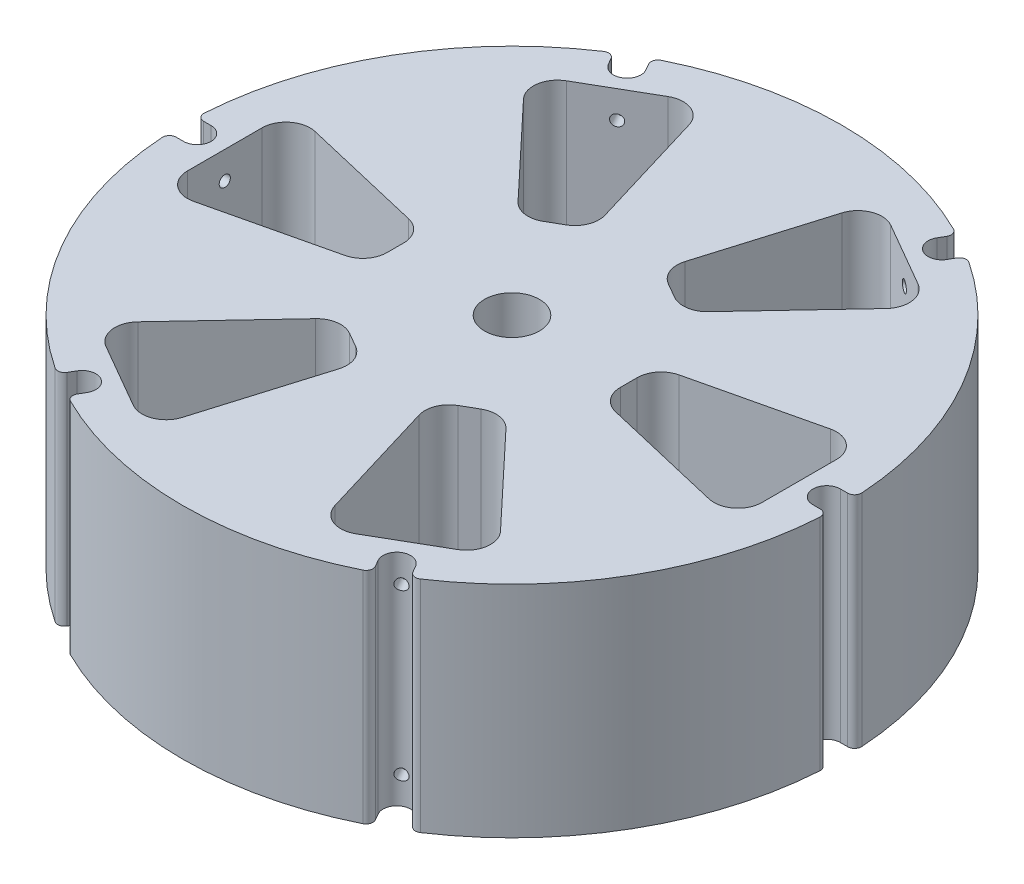
SolidWorks part; units mm, degrees
material "6061-T6 (SS)"
ref_plane "Front Plane" through (0, 0, 0) normal (0, 0, 1) x (1, 0, 0)
ref_plane "Top Plane" through (0, 0, 0) normal (0, 1, 0) x (1, 0, 0)
ref_plane "Right Plane" through (0, 0, 0) normal (1, 0, 0) x (0, 0, -1)
sketch "Sketch1" plane through (0, 0, 0) normal (0, 1, 0) x (1, 0, 0)
  circle A0 centre (0, 0) radius 76.2
  circle A1 centre (0, 0) radius 14.2875
  dimension "D1" = 152.4
  dimension "D2" = 28.575
extrude "Boss-Extrude1" add sketch "Sketch1" against normal mid plane 50.8
sketch "Sketch3" plane through (0, -25.4, 0) normal (0, -1, 0) x (-1, 0, 0)
  line L0 (-76.1338, 3.175) -> (-72.771, 3.175)
  line L1 (-76.1338, -3.175) -> (-72.771, -3.175)
  circle A0 centre (0, 0) radius 76.2 construction
  arc A1 (-72.771, 3.175) -> (-72.771, -3.175) centre (-72.771, 0) cw
  arc A2 (-76.1338, -3.175) -> (-76.1338, 3.175) centre (0, 0) cw
  point P9 (-69.596, 0)
  point P13 (-76.2, 0)
  dimension "D1" = 6.35
  dimension "D2" = 6.604
extrude "Cut-Extrude1" cut sketch "Sketch3" against normal through all
sketch "Sketch4" plane through (0, -25.4, 0) normal (0, -1, 0) x (-1, 0, 0)
  line L0 (-66.421, 15.6285) -> (-66.421, -15.6285)
  line L1 (-66.421, -15.6285) -> (-26.9875, -6.35)
  line L2 (-26.9875, -6.35) -> (-26.9875, 6.35)
  line L3 (-26.9875, 6.35) -> (-66.421, 15.6285)
  line L4 (-66.421, 0) -> (0, 0) construction
  line L5 (-26.9875, -6.35) -> (0, 0) construction
  circle A2 centre (0, 0) radius 14.2875 construction
  point P12 (-14.2875, 0)
  point P14 (-26.9875, 0)
  dimension "D1" = 3.175
  dimension "D2" = 12.7
  dimension "D4" = 12.7
extrude "Cut-Extrude2" cut sketch "Sketch4" against normal through all
hole_wizard "#5-40 Tapped Hole1" positions "Sketch5" profile "Sketch6" tap size "#5-40" standard "ANSI Inch" end condition through all
sketch "Sketch5" plane through (66.421, 0, 0) normal (-1, 0, 0) x (0, 0, 1)
  line L0 (-15.6285, -25.4) -> (15.6285, -25.4) construction
  point P0 (0, -19.05)
  dimension "D1" = 6.35
sketch "Sketch6" plane through (66.421, -19.05, 0) normal (0, 1, 0) x (0, 0, 1)
  line L0 (0, 0) -> (0, 9.7128)
  line L1 (0, 9.7128) -> (1.289, 9.7128)
  line L2 (1.289, 9.7128) -> (1.289, 0)
  line L5 (1.289, 0) -> (0, 0)
  line L11 (0, -6.35) -> (0, 107.95) construction
  dimension "Thru Tap Drill Dia." = 2.5781
  dimension "Thru Tap Drill Depth" = 9.7128
cosmetic thread "Hole Thread1" parameters "D2"=3.175
fillet "Fillet1" radius 1.5875 2 edges at (76.1338, 0, 3.175) (76.1338, 0, -3.175)
fillet "Fillet2" radius 5.5562 4 edges at (66.421, 0, 15.6285) (66.421, 0, -15.6285) (26.9875, 0, 6.35) (26.9875, 0, -6.35)
mirror "Mirror1" about plane through (0, 0, 0) normal (0, 1, 0) of "#5-40 Tapped Hole1"
cosmetic thread "Hole Thread7" parameters "D2"=3.175
pattern_circular "CirPattern1" count 6 over 360 about axis through (0, -25.4, 0) along (0, 1, 0) of "Cut-Extrude1", "Cut-Extrude2", "Fillet2", "Fillet1", "#5-40 Tapped Hole1", "Mirror1"
cosmetic thread "Hole Thread2" parameters "D2"=3.175
cosmetic thread "Hole Thread3" parameters "D2"=3.175
cosmetic thread "Hole Thread4" parameters "D2"=3.175
cosmetic thread "Hole Thread5" parameters "D2"=3.175
cosmetic thread "Hole Thread6" parameters "D2"=3.175
cosmetic thread "Hole Thread8" parameters "D2"=3.175
cosmetic thread "Hole Thread9" parameters "D2"=3.175
cosmetic thread "Hole Thread10" parameters "D2"=3.175
cosmetic thread "Hole Thread11" parameters "D2"=3.175
cosmetic thread "Hole Thread12" parameters "D2"=3.175
sketch "Sketch7" plane through (0, 25.4, 0) normal (0, 1, 0) x (1, 0, 0)
  circle A0 centre (0, 0) radius 6.35
  circle A1 centre (0, 0) radius 14.2875
  circle A2 centre (0, 0) radius 14.2875 construction
  dimension "D1" = 12.7
extrude "Boss-Extrude2" add sketch "Sketch7" against normal offset from surface (10.668 mm away) 40.132 up to face at (23.0798, -25.4, 39.9754)
sketch "Sketch8" plane through (0, -25.4, 0) normal (0, -1, 0) x (1, 0, 0)
  circle A0 centre (0, 0) radius 25.4
  dimension "D1" = 50.8
extrude "Cut-Extrude3" cut sketch "Sketch8" against normal blind 25.4
